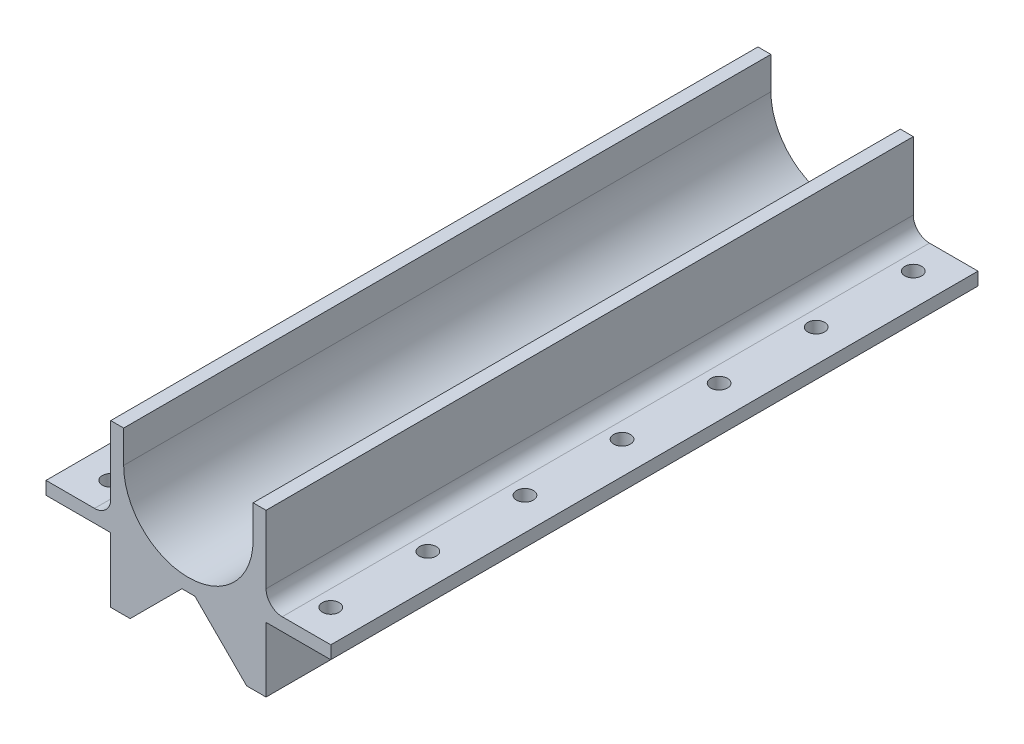
SolidWorks part; units mm, degrees
material "Custom Plastic"
ref_plane "Front Plane" through (0, 0, 0) normal (0, 0, 1) x (1, 0, 0)
ref_plane "Top Plane" through (0, 0, 0) normal (0, 1, 0) x (1, 0, 0)
ref_plane "Right Plane" through (0, 0, 0) normal (1, 0, 0) x (0, 0, -1)
sketch "Sketch1" plane through (0, 0, 0) normal (0, 0, 1) x (1, 0, 0)
  line L0 (0, 0) -> (0, 30) construction
  line L1 (-20, 20) -> (-20, 30)
  line L2 (-20, 30) -> (-24, 30)
  line L3 (-24, 30) -> (-24, 4)
  line L4 (-24, 4) -> (-44, 4)
  line L5 (-44, 4) -> (-44, 0)
  line L6 (-44, 0) -> (-24, 0)
  line L7 (-24, 0) -> (-24, -20)
  line L8 (-24, -20) -> (-20, -20)
  line L9 (-20, -20) -> (-20, -4)
  line L10 (-20, -4) -> (20, -4)
  line L11 (0, -4) -> (0, 0) construction
  line L12 (20, -20) -> (20, -4)
  line L13 (24, -20) -> (20, -20)
  line L14 (24, 0) -> (24, -20)
  line L15 (44, 0) -> (24, 0)
  line L16 (44, 4) -> (44, 0)
  line L17 (24, 4) -> (44, 4)
  line L18 (24, 30) -> (24, 4)
  line L19 (20, 30) -> (24, 30)
  line L20 (20, 20) -> (20, 30)
  arc A0 (-20, 20) -> (20, 20) centre (0, 20) ccw
  dimension "D1" = 20
  dimension "D2" = 10
  dimension "D3" = 4
  dimension "D4" = 4
  dimension "D5" = 20
extrude "Boss-Extrude1" add sketch "Sketch1" along normal blind 200
fillet "Fillet1" radius 5 2 edges at (24, 4, 100) (-24, 4, 100)
chamfer "Chamfer1" distance 18 angle 45 2 edges at (20, -4, 100) (-20, -4, 100)
sketch "Sketch2" plane through (0, 0, 0) normal (0, -1, 0) x (1, 0, 0)
  line L0 (-34, 200) -> (-34, 0) construction
  line L1 (-44, 200) -> (-24, 200) construction
  line L2 (-44, 0) -> (-24, 0) construction
  line L3 (0, 200) -> (0, 0) construction
  line L4 (-2, 200) -> (2, 200) construction
  line L5 (-2, 0) -> (2, 0) construction
  circle A0 centre (-34, 190) radius 2.6
  circle A1 centre (-34, 160) radius 2.6
  circle A2 centre (-34, 130) radius 2.6
  circle A3 centre (-34, 100) radius 2.6
  circle A4 centre (-34, 70) radius 2.6
  circle A5 centre (-34, 40) radius 2.6
  circle A6 centre (-34, 10) radius 2.6
  circle A7 centre (34, 10) radius 2.6
  circle A8 centre (34, 40) radius 2.6
  circle A9 centre (34, 70) radius 2.6
  circle A10 centre (34, 100) radius 2.6
  circle A11 centre (34, 130) radius 2.6
  circle A12 centre (34, 160) radius 2.6
  circle A13 centre (34, 190) radius 2.6
  dimension "D1" = 5.2
  dimension "D2" = 10
  dimension "D4" = 30
  dimension "D3" = 7
extrude "Cut-Extrude1" cut sketch "Sketch2" against normal through all
